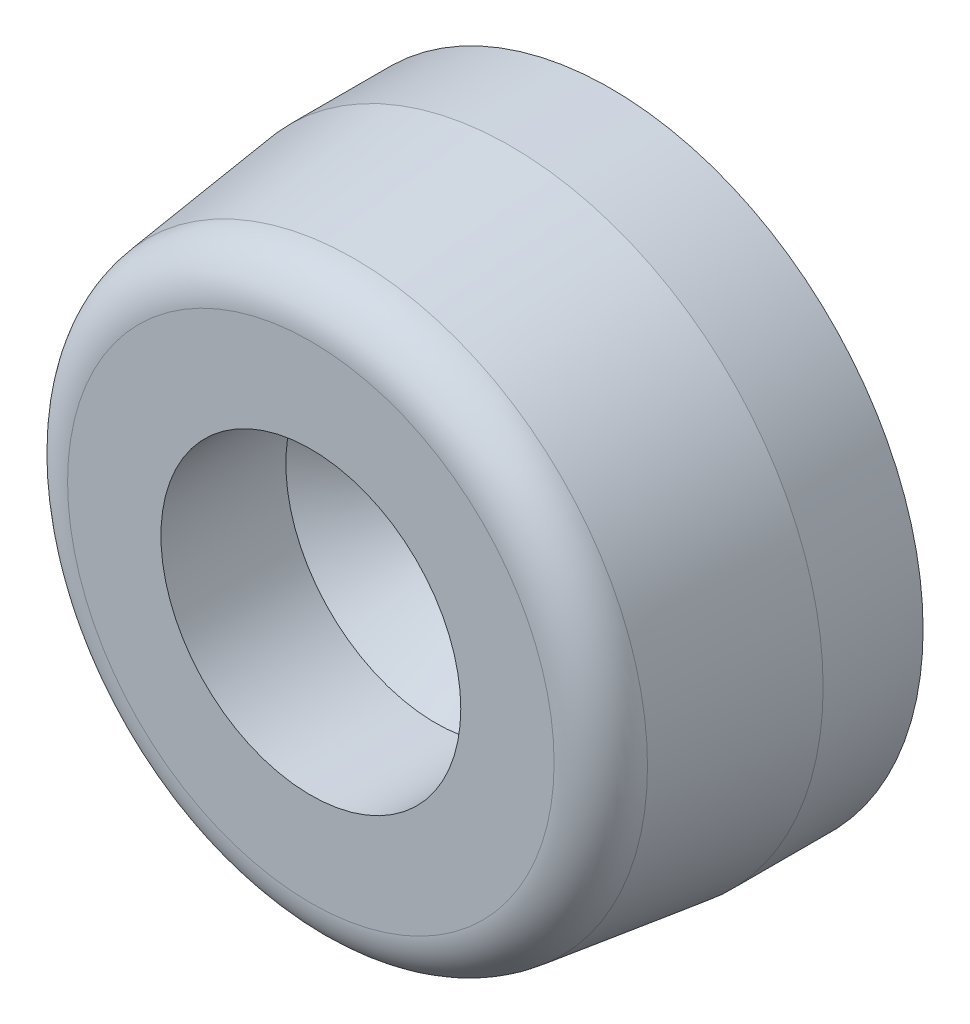
SolidWorks part; units mm, degrees
ref_plane "Plan de face" through (0, 0, 0) normal (0, 0, 1) x (1, 0, 0)
ref_plane "Plan de dessus" through (0, 0, 0) normal (0, 1, 0) x (1, 0, 0)
ref_plane "Plan de droite" through (0, 0, 0) normal (1, 0, 0) x (0, 0, -1)
sketch "Esquisse1" plane through (0, 0, 0) normal (0, 0, 1) x (1, 0, 0)
  circle A0 centre (0, 0) radius 12.5
  circle A1 centre (0, 0) radius 3
  dimension "D1" = 6
  dimension "D2" = 25
extrude "Boss.-Extru.1" add sketch "Esquisse1" along normal blind 12
chamfer "Chanfrein3" distance 8 distance2 1 1 edges at (12.5, 0, 12) first distance on face at (12.5, 0, 12)
sketch "Esquisse3" plane through (0, 0, 12) normal (0, 0, 1) x (1, 0, 0)
  circle A0 centre (0, 0) radius 6
  dimension "D1" = 12
extrude "Enlèv. mat.-Extru.2" cut sketch "Esquisse3" against normal blind 5
chamfer "Chanfrein4" distance 3 angle 45 1 edges at (3, 0, 7)
fillet "Congé2" radius 2 1 edges at (11.5, 0, 12)
